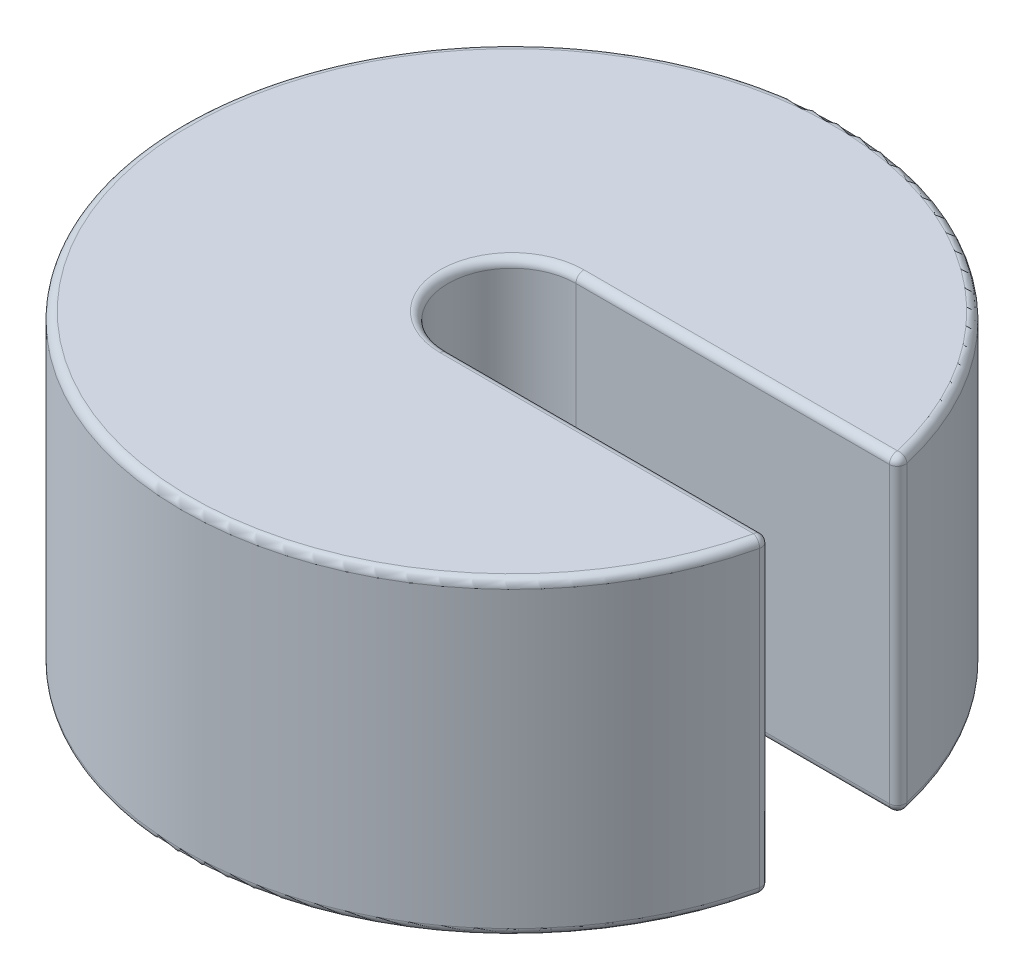
SolidWorks part; units mm, degrees
ref_plane "Front Plane" through (0, 0, 0) normal (0, 0, 1) x (1, 0, 0)
ref_plane "Top Plane" through (0, 0, 0) normal (0, 1, 0) x (1, 0, 0)
ref_plane "Right Plane" through (0, 0, 0) normal (1, 0, 0) x (0, 0, -1)
sketch "Sketch1" plane through (0, 0, 0) normal (0, 1, 0) x (1, 0, 0)
  line L0 (0, 8.05) -> (40.7118, 8.05)
  line L1 (0, -8.05) -> (40.7118, -8.05)
  arc A0 (0, 8.05) -> (0, -8.05) centre (0, 0) ccw
  arc A1 (40.7118, 8.05) -> (40.7118, -8.05) centre (0, 0) ccw
  arc A2 (0, -8.05) -> (0, 8.05) centre (0, 0) ccw construction
  arc A3 (40.7118, -8.05) -> (40.7118, 8.05) centre (0, 0) ccw construction
  dimension "D1" = 16.1
  dimension "D2" = 83
extrude "Boss-Extrude1" add sketch "Sketch1" along normal blind 39
fillet "Fillet1" radius 1 10 edges at (-41.5, 0, 0) (-8.05, 0, 0) (-41.5, 39, 0) (-8.05, 39, 0) (40.7118, 19.5, 8.05) (20.3559, 39, 8.05) (20.3559, 0, 8.05) (20.3559, 39, -8.05) (40.7118, 19.5, -8.05) (20.3559, 0, -8.05)
